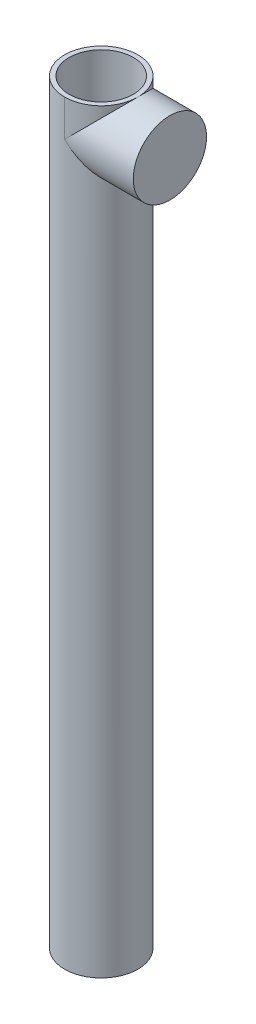
SolidWorks part; units mm, degrees
material "STD Carbon Fibre"
ref_plane "Front Plane" through (0, 0, 0) normal (0, 0, 1) x (1, 0, 0)
ref_plane "Top Plane" through (0, 0, 0) normal (0, 1, 0) x (1, 0, 0)
ref_plane "Right Plane" through (0, 0, 0) normal (1, 0, 0) x (0, 0, -1)
sketch "Sketch1" plane through (0, 0, 0) normal (0, 0, 1) x (1, 0, 0)
  line L0 (8, 82.5) -> (0, 82.5)
  line L1 (8, 82.5) -> (8, -82.5)
  line L2 (0, 82.5) -> (0, -82.5)
  line L3 (0, -82.5) -> (8, -82.5)
  line L4 (0, 82.5) -> (0, -82.5) construction
  point P5 (8, 0)
  dimension "D1" = 165
  dimension "D2" = 8
revolve "Revolve1" add sketch "Sketch1" angle 360 about L2
sketch "Sketch4" plane through (0, 0, 0) normal (1, 0, 0) x (0, 0, -1)
  line L0 (8, -82.5) -> (8, 82.5) construction
  line L1 (8, 82.5) -> (-8, 82.5) construction
  circle A0 centre (0, 74.5) radius 8
  point P6 (0, 0)
extrude "Boss-Extrude1" add sketch "Sketch4" along normal blind 15
sketch "Sketch3" plane through (0, 82.5, 0) normal (0, 1, 0) x (1, 0, 0)
  circle A0 centre (0, 0) radius 7
  dimension "D1" = 14
extrude "Cut-Extrude1" cut sketch "Sketch3" against normal through all
